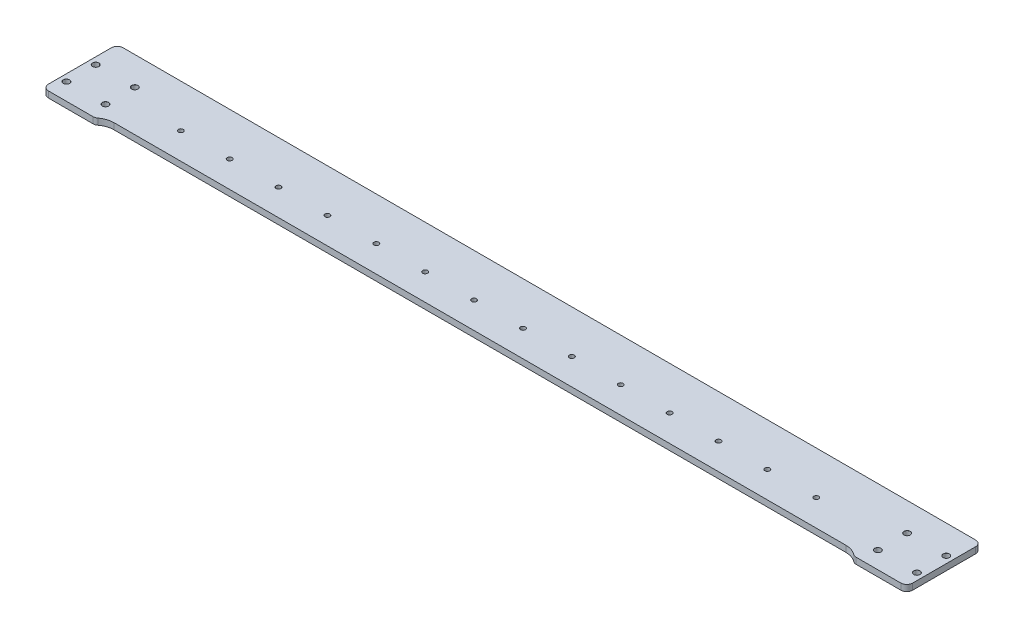
SolidWorks part; units mm, degrees
material "AISI 1045 Steel, cold drawn"
ref_plane "Front Plane" through (0, 0, 0) normal (0, 0, 1) x (1, 0, 0)
ref_plane "Top Plane" through (0, 0, 0) normal (0, 1, 0) x (1, 0, 0)
ref_plane "Right Plane" through (0, 0, 0) normal (1, 0, 0) x (0, 0, -1)
sketch "Sketch1" plane through (0, 0, 0) normal (0, 1, 0) x (1, 0, 0)
  line L0 (0, 0) -> (194, 0)
  line L1 (194, 0) -> (194, -2.7)
  line L2 (194, -2.7) -> (221, -2.7)
  line L3 (221, -2.7) -> (221, 29.7)
  line L4 (221, 29.7) -> (0, 29.7) construction
  line L7 (0, 0) -> (0, 29.7)
  line L8 (221, 13.5) -> (0, 13.5) construction
  line L9 (221, 29.7) -> (221, 35.5)
  line L10 (221, 35.5) -> (0, 35.5)
  line L11 (0, 35.5) -> (0, 29.7)
  dimension "D1" = 194
  dimension "D2" = 27
  dimension "D3" = 29.7
  dimension "D4" = 32.4
  dimension "D5" = 22
extrude "Boss-Extrude1" add sketch "Sketch1" along normal blind 3.175
hole_wizard "M3 Clearance Hole1" positions "Sketch2" profile "Sketch3" hole size "M3" standard "ANSI Metric" end condition through all
sketch "Sketch2" plane through (0, 3.175, 0) normal (0, 1, 0) x (1, 0, 0)
  line L1 (217.5, 6) -> (197.5, 6)
  line L2 (217.5, 6) -> (217.5, 21)
  line L3 (217.5, 21) -> (197.5, 21)
  line L4 (197.5, 6) -> (197.5, 21)
  line L5 (217.5, 6) -> (197.5, 21) construction
  line L6 (217.5, 21) -> (197.5, 6) construction
  line L10 (207.5, 13.5) -> (207.5, -2.7) construction
  line L13 (194, -2.7) -> (221, -2.7) construction
  line L17 (0, 0) -> (194, 0) construction
  point P2 (197.5, 21)
  point P35 (217.5, 6)
  point P36 (217.5, 21)
  point P37 (197.5, 6)
  dimension "D1" = 20
  dimension "D2" = 13.5
  dimension "D3" = 15
sketch "Sketch3" plane through (197.5, 3.175, -21) normal (1, 0, 0) x (0, 0, 1)
  line L0 (0, 0) -> (0, 3.175)
  line L1 (0, 3.175) -> (1.6, 3.175)
  line L2 (1.6, 3.175) -> (1.6, 0.025)
  line L3 (1.6, 0.025) -> (1.625, 0)
  line L5 (1.625, 0) -> (0, 0)
  line L6 (-1.6, 0.025) -> (-1.625, 0) construction
  line L11 (0, -6.35) -> (0, 107.95) construction
  dimension "Thru Hole Dia." = 3.2
  dimension "Thru Hole Depth" = 3.175
  dimension "Near C'Sink Dia." = 3.25
  dimension "Near C'Sink Angle" = 90
fillet "Fillet1" radius 10 1 edges at (194, 1.5875, 0)
fillet "Fillet2" radius 3 3 edges at (221, 1.5875, 2.7) (194, 1.5875, 2.7) (221, 1.5875, -35.5)
mirror "Mirror1" about plane through (0, 3.175, -35.5) normal (1, 0, 0) of bodies 103
hole_wizard "Tap Drill for M3x0.5 Tap2" positions "Sketch6" profile "Sketch7" hole size "M3x0.5" standard "ANSI Metric" end condition through all
sketch "Sketch6" plane through (0, 0, 0) normal (0, -1, 0) x (-1, 0, 0)
  line L0 (187.1655, 0) -> (-187.1655, 0) construction
  line L2 (221, 0.3) -> (221, 32.5) construction
  point P11 (166.5, 13.5)
  dimension "D1" = 13.5
  dimension "D2" = 54.5
sketch "Sketch7" plane through (-166.5, 0, -13.5) normal (1, 0, 0) x (0, 0, -1)
  line L0 (0, 0) -> (0, 3.175)
  line L1 (0, 3.175) -> (1.25, 3.175)
  line L2 (1.25, 3.175) -> (1.25, 0.025)
  line L3 (1.25, 0.025) -> (1.275, 0)
  line L5 (1.275, 0) -> (0, 0)
  line L6 (-1.25, 0.025) -> (-1.275, 0) construction
  line L11 (0, -6.35) -> (0, 107.95) construction
  dimension "Thru Hole Dia." = 2.5
  dimension "Thru Hole Depth" = 3.175
  dimension "Near C'Sink Dia." = 2.55
  dimension "Near C'Sink Angle" = 90
pattern_linear "LPattern1" count 14 spacing 25 along (1, 0, 0) of "Tap Drill for M3x0.5 Tap2"
